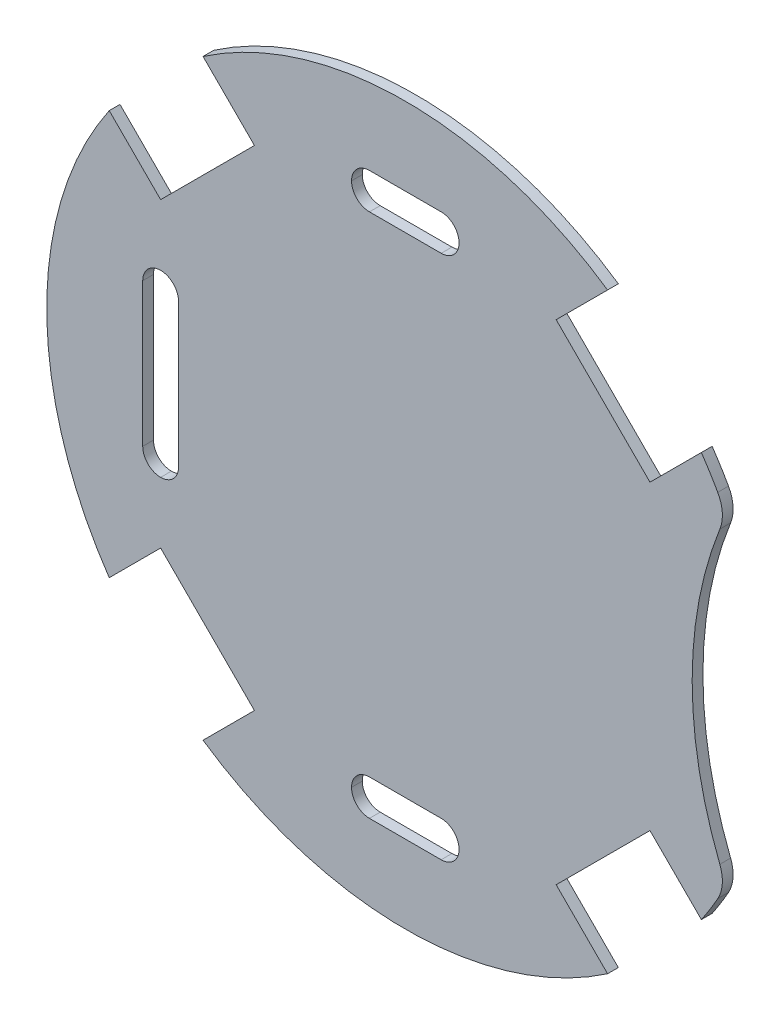
SolidWorks part; units mm, degrees
ref_plane "Alzado" through (0, 0, 0) normal (0, 0, 1) x (1, 0, 0)
ref_plane "Planta" through (0, 0, 0) normal (0, 1, 0) x (1, 0, 0)
ref_plane "Vista lateral" through (0, 0, 0) normal (1, 0, 0) x (0, 0, -1)
sketch "Croquis1" plane through (0, 0, 0) normal (0, 0, 1) x (1, 0, 0)
  circle A0 centre (0, 0) radius 100
  dimension "D1" = 200
extrude "Saliente-Extruir1" add sketch "Croquis1" along normal blind 3
sketch "Croquis3" plane through (0, 0, 3) normal (0, 0, 1) x (1, 0, 0)
  line L0 (0, 0) -> (190, 0) construction
  circle A0 centre (190, 0) radius 110
  dimension "D1" = 220
  dimension "D2" = 190
extrude "Cortar-Extruir1" cut sketch "Croquis3" against normal blind 3
fillet "Redondeo1" radius 10 2 edges at (89.4737, -44.6594, 1.5) (89.4737, 44.6594, 1.5)
sketch "Croquis4" plane through (0, 0, 3) normal (0, 0, 1) x (1, 0, 0)
  line L0 (0, 0) -> (-70.7107, -70.7107) construction
  line L1 (-57.6292, -83.7922) -> (-83.7922, -57.6292)
  line L2 (-57.6292, 83.7922) -> (-42.0729, 68.2358)
  line L3 (-83.7922, -57.6292) -> (-68.2358, -42.0729)
  line L4 (-68.2358, -42.0729) -> (-42.0729, -68.2358)
  line L5 (-42.0729, -68.2358) -> (-57.6292, -83.7922)
  line L6 (-42.0729, 68.2358) -> (-68.2358, 42.0729)
  line L7 (-68.2358, 42.0729) -> (-83.7922, 57.6292)
  line L8 (-83.7922, 57.6292) -> (-57.6292, 83.7922)
  line L9 (83.7922, 57.6292) -> (68.2358, 42.0729)
  line L10 (68.2358, 42.0729) -> (42.0729, 68.2358)
  line L11 (42.0729, 68.2358) -> (57.6292, 83.7922)
  line L12 (57.6292, 83.7922) -> (83.7922, 57.6292)
  line L13 (57.6292, -83.7922) -> (42.0729, -68.2358)
  line L14 (42.0729, -68.2358) -> (68.2358, -42.0729)
  line L15 (68.2358, -42.0729) -> (83.7922, -57.6292)
  line L16 (83.7922, -57.6292) -> (57.6292, -83.7922)
  arc A0 (87.1345, 49.0671) -> (87.1345, -49.0671) centre (0, 0) ccw construction
  point P25 (0, 0)
  dimension "D3" = 18.5
  dimension "D4" = 78
  dimension "D1" = 22
  dimension "D2" = 37
  dimension "D5" = 4
extrude "Cortar-Extruir2" cut sketch "Croquis4" against normal through all
sketch "Croquis6" plane through (0, 0, 3) normal (0, 0, 1) x (1, 0, 0)
  line L0 (-68.2358, -42.0729) -> (-68.1778, 42.4239) construction
  line L3 (-42.0729, -68.2358) -> (42.0729, -68.2358) construction
  line L4 (-63.2358, -25) -> (-63.2358, 25)
  line L5 (-63.2358, 0) -> (0, 0) construction
  line L6 (-63.2358, 25) -> (-73.2358, 25)
  line L7 (-73.2358, 25) -> (-73.2358, -25)
  line L8 (-73.2358, -25) -> (-63.2358, -25)
  line L12 (-15, 78.24) -> (15, 78.24)
  line L13 (-15, 68.24) -> (-15, 78.24)
  line L14 (-15, 68.24) -> (15, 68.24)
  line L15 (15, 78.24) -> (15, 68.24)
  line L19 (-15, -68.24) -> (-15, -78.24)
  line L20 (-15, -78.24) -> (15, -78.24)
  line L21 (-15, -68.24) -> (15, -68.24)
  line L22 (15, -78.24) -> (15, -68.24)
  line L23 (0, 0) -> (0, -68.24) construction
  arc A1 (-82.5716, 56.4086) -> (-82.5716, -56.4086) centre (0, 0) ccw construction
  arc A2 (-56.4086, -82.5716) -> (56.4086, -82.5716) centre (0, 0) ccw construction
  point P44 (0, 0)
  dimension "D1" = 63.2358
  dimension "D2" = 10
  dimension "D3" = 73.2358
  dimension "D4" = 50
  dimension "D5" = 25
  dimension "D6" = 68.24
  dimension "D7" = 10
  dimension "D8" = 30
  dimension "D9" = 15
  dimension "D10" = 78.24
extrude "Cortar-Extruir4" cut sketch "Croquis6" against normal blind 10
fillet "Redondeo3" radius 5 12 edges at (15, -78.24, 1.5) (-15, -78.24, 1.5) (15, -68.24, 1.5) (-15, -68.24, 1.5) (-73.2358, -25, 1.5) (-63.2358, -25, 1.5) (-73.2358, 25, 1.5) (-63.2358, 25, 1.5) (-15, 68.24, 1.5) (15, 68.24, 1.5) (-15, 78.24, 1.5) (15, 78.24, 1.5)
